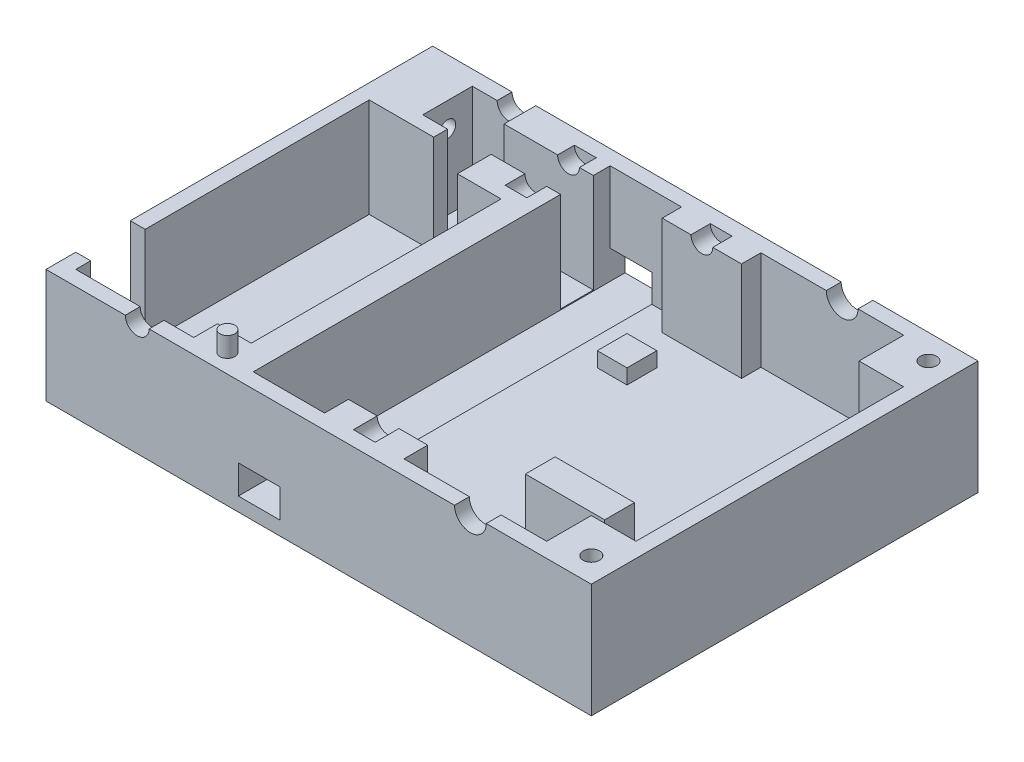
SolidWorks part; units mm, degrees
ref_plane "前视基准面" through (0, 0, 0) normal (0, 0, 1) x (1, 0, 0)
ref_plane "上视基准面" through (0, 0, 0) normal (0, 1, 0) x (1, 0, 0)
ref_plane "右视基准面" through (0, 0, 0) normal (1, 0, 0) x (0, 0, -1)
other "Configuration Table"
sketch "草图1" plane through (0, 0, 0) normal (0, 1, 0) x (1, 0, 0)
  line L1 (-27.5, 19.5) -> (27.5, 19.5)
  line L2 (-27.5, 19.5) -> (-27.5, -19.5)
  line L3 (-27.5, -19.5) -> (27.5, -19.5)
  line L4 (27.5, 19.5) -> (27.5, -19.5)
  line L5 (-27.5, 19.5) -> (27.5, -19.5) construction
  line L6 (-27.5, -19.5) -> (27.5, 19.5) construction
  point P0 (0, 0)
  dimension "D1" = 55
  dimension "D2" = 39
extrude "凸台-拉伸1" add sketch "草图1" along normal blind 11.5
shell "抽壳1" thickness 1.5 removed face at (0, 11.5, 0)
sketch "草图2" plane through (0, 0, -19.5) normal (0, 0, -1) x (-1, 0, 0)
  line L0 (7.9, 1.6) -> (4.1, 1.6) construction
  line L1 (3.9, 4.3) -> (8.1, 4.3)
  line L2 (3.9, 4.3) -> (3.9, 1.4)
  line L3 (3.9, 1.4) -> (8.1, 1.4)
  line L4 (8.1, 4.3) -> (8.1, 1.4)
  line L5 (7.9, 1.6) -> (7.9, 4.1) construction
  line L6 (7.9, 4.1) -> (4.1, 4.1) construction
  line L7 (4.1, 1.6) -> (4.1, 4.1) construction
  circle A0 centre (-15.3, 11.5) radius 1.6
  circle A1 centre (18.3, 11.5) radius 1.2
  circle A2 centre (-15.3, 11.5) radius 1.5 construction
  circle A3 centre (18.3, 11.5) radius 1 construction
  dimension "D1" = 0.1
  dimension "D2" = 0.2
  dimension "D3" = 0.2
  dimension "D4" = 0.2
  dimension "D5" = 0.2
  dimension "D6" = 0.2
extrude "切除-拉伸1" cut sketch "草图2" against normal through all
sketch "草图3" plane through (0, 1.5, 0) normal (0, 1, 0) x (1, 0, 0)
  line L0 (-25.8, -15.5) -> (-10.8, -15.5) construction
  line L5 (-10.7, 9.6) -> (-10.7, -15.6)
  line L6 (-15.1, 13) -> (-8.1, 13)
  line L7 (-15.1, 13) -> (-15.1, 9.6)
  line L8 (-15.1, 9.6) -> (-10.7, 9.6)
  line L10 (-17.1, -18) -> (13.7, -18) construction
  line L11 (-10.7, -18) -> (-8.1, -18)
  line L13 (-14.3, -17.8) -> (-14.3, -15.5) construction
  line L16 (-15.3, 9.5) -> (-15.3, 11.5) construction
  line L17 (-10.8, 9.5) -> (-10.8, -15.5) construction
  line L18 (-8.1, 18) -> (-8.1, -18) construction
  line L19 (13.7, 18) -> (-17.1, 18) construction
  line L20 (-17.1, 18) -> (-8.1, 18)
  line L21 (-17.1, 18) -> (-17.1, 16.3)
  line L22 (-17.1, 16.3) -> (-8.1, 16.3)
  line L23 (-8.1, 18) -> (-8.1, 16.3)
  line L24 (-17.1, 18) -> (-17.1, 19.5) construction
  line L25 (-8.1, 13) -> (-8.1, -18)
  line L26 (4.6159, 15.85) -> (4.2435, 15.85) construction
  line L27 (-0.9, 18) -> (7.1, 18)
  line L28 (-0.9, 18) -> (-0.9, 16.05)
  line L29 (-0.9, 16.05) -> (7.1, 16.05)
  line L30 (7.1, 18) -> (7.1, 16.05)
  line L31 (4.1, -18.1452) -> (4.1, 18.1548) construction
  line L32 (-17.1, -18) -> (13.7, -18) construction
  line L33 (-0.9, -15.6) -> (7.1, -15.6)
  line L34 (-0.9, -15.6) -> (-0.9, -18)
  line L35 (-0.9, -18) -> (7.1, -18)
  line L36 (7.1, -15.6) -> (7.1, -18)
  line L38 (26, 18) -> (16.9, 18) construction
  line L39 (21.5, 18) -> (26, 18)
  line L40 (21.5, 18) -> (21.5, 13.5)
  line L41 (21.5, 13.5) -> (26, 13.5)
  line L42 (26, 18) -> (26, 13.5)
  line L43 (26, -18) -> (26, 18) construction
  line L44 (-26, 18) -> (-26, -18) construction
  line L45 (21.5, -13.5) -> (26, -13.5)
  line L46 (21.5, -13.5) -> (21.5, -18)
  line L47 (21.5, -18) -> (26, -18)
  line L48 (26, -13.5) -> (26, -18)
  line L49 (-26, 18) -> (-22, 18)
  line L50 (-26, 18) -> (-26, 13)
  line L52 (-22, 18) -> (-22, 13)
  line L53 (-26, 11.6) -> (-19.5, 11.6)
  line L54 (-26, 11.6) -> (-26, 13)
  line L55 (-22, 13) -> (-19.5, 13)
  line L56 (-19.5, 11.6) -> (-19.5, 13)
  line L57 (-15.3, 11.5) -> (-21.3, 11.5) construction
  line L58 (-19.3, 19) -> (-19.3, 11.5) construction
  line L59 (-10.8, 9.5) -> (-25.8, 9.5) construction
  line L60 (-19.5, 18) -> (-26, 18) construction
  line L62 (-14.1, -15.6) -> (-10.7, -15.6)
  line L63 (-14.1, -15.6) -> (-14.1, -18)
  line L64 (-14.1, -18) -> (-10.7, -18)
  dimension "D2" = 4
  dimension "D3" = 0.1
  dimension "D4" = 0.2
  dimension "D5" = 1.7
  dimension "D6" = 0.1
  dimension "D7" = 8
  dimension "D8" = 0.2
  dimension "D9" = 3
  dimension "D10" = 8
  dimension "D11" = 3
  dimension "D12" = 2.4
  dimension "D13" = 4.5
  dimension "D14" = 4.5
  dimension "D15" = 4.5
  dimension "D16" = 4.5
  dimension "D17" = 0.2
  dimension "D18" = 0.1
  dimension "D19" = 5
  dimension "D20" = 0.1
  dimension "D21" = 0.2
extrude "凸台-拉伸2" add sketch "草图3" along normal up to surface (10 mm away) up to face at (-23.125, 11.5, 0)
sketch "草图4" plane through (0, 0, 19.5) normal (0, 0, 1) x (1, 0, 0)
  circle A0 centre (3.1, 11.5) radius 1.1
  circle A1 centre (3.1, 11.5) radius 1 construction
  dimension "D1" = 0.1
extrude "切除-拉伸2" cut sketch "草图4" against normal offset from surface (36 mm away) 1.5 from offset 1.5 up to face at (-6, 2.85, -19.5) offset against normal yes
sketch "草图5" plane through (0, 0, -19.5) normal (0, 0, -1) x (-1, 0, 0)
  circle A0 centre (10.6, 11.5) radius 1.1
  circle A1 centre (10.6, 11.5) radius 1 construction
  dimension "D1" = 0.1
extrude "切除-拉伸3" cut sketch "草图5" against normal blind 7 from offset 1.5 offset against normal yes
sketch "草图6" plane through (0, 1.5, 0) normal (0, 1, 0) x (1, 0, 0)
  line L0 (-0.9, 18) -> (-8.1, 18) construction
  line L1 (-1.1, 12.7) -> (1.9, 12.7)
  line L2 (-1.1, 12.7) -> (-1.1, 9.7)
  line L3 (-1.1, 9.7) -> (1.9, 9.7)
  line L4 (1.9, 12.7) -> (1.9, 9.7)
  line L6 (-8.1, -18) -> (-8.1, 13) construction
  line L8 (-32, 4) -> (-27.5, 4)
  line L9 (-32, 4) -> (-32, -4)
  line L10 (-32, -4) -> (-27.5, -4)
  line L11 (-27.5, 4) -> (-27.5, -4)
  line L14 (-27.5, 0) -> (-45.462, 0) construction
  line L15 (-27.5, 19.5) -> (-27.5, -19.5) construction
  dimension "D1" = 8.3
  dimension "D2" = 3
  dimension "D3" = 3
  dimension "D4" = 7
  dimension "D5" = 4.5
  dimension "D6" = 8
extrude "变速卡位凸台-拉伸3" add sketch "草图6" along normal blind 1.5 and the other way blind 1.5
sketch "草图7" plane through (0, 0, 0) normal (0, -1, 0) x (1, 0, 0)
  line L0 (-32, -4) -> (-32, 4) construction
  line L1 (27.5, 0) -> (56.3628, 0) construction
  line L2 (27.5, 19.5) -> (27.5, -19.5) construction
  line L3 (21.5, 13.5) -> (21.5, 18) construction
  line L4 (26, 13.5) -> (21.5, 13.5) construction
  circle A0 centre (-29.8, 0) radius 1
  circle A1 centre (25, 17) radius 0.825
  circle A2 centre (25, -17) radius 0.825
  dimension "D1" = 2
  dimension "D2" = 2.2
  dimension "D3" = 1.65
  dimension "D4" = 3.5
  dimension "D5" = 3.5
extrude "盖子固定切除-拉伸4" cut sketch "草图7" against normal through all
sketch "草图8" plane through (0, 1.5, 0) normal (0, 1, 0) x (1, 0, 0)
  line L0 (27.5, 0) -> (45.6897, 0) construction
  line L1 (27.5, -19.5) -> (27.5, 19.5) construction
  line L2 (26, -13.5) -> (26, 13.5) construction
  line L3 (26, -13.5) -> (21.5, -13.5) construction
  circle A0 centre (23, 7.6) radius 1
  circle A1 centre (23, -10.5) radius 1
  dimension "D1" = 2
  dimension "D2" = 3
  dimension "D3" = 3
  dimension "D4" = 2
  dimension "D5" = 3
  dimension "D6" = 3
extrude "底部螺丝孔切除-拉伸5" cut sketch "草图8" against normal through all
sketch "草图9" plane through (-27.5, 0, 0) normal (-1, 0, 0) x (0, 0, 1)
  line L0 (-19.5, 11.5) -> (19.5, 11.5) construction
  line L1 (-18, 11.5) -> (-18, 1.5) construction
  circle A0 centre (-15.502, 9) radius 0.825
  dimension "D1" = 1.65
  dimension "D2" = 2.5
  dimension "D3" = 2.498
extrude "前螺丝孔切除-拉伸6" cut sketch "草图9" against normal up to next
sketch "草图10" plane through (0, 1.5, 0) normal (0, 1, 0) x (1, 0, 0)
  line L0 (16.8, -26.9936) -> (16.8, 34.2064) construction
  line L1 (11.55, -7.2) -> (19.55, -7.2)
  line L2 (11.55, -7.2) -> (11.55, -10.2)
  line L3 (11.55, -10.2) -> (19.55, -10.2)
  line L4 (19.55, -7.2) -> (19.55, -10.2)
  line L5 (17.8373, -7.1) -> (18.6564, -7.1) construction
  dimension "D1" = 8
  dimension "D2" = 2.75
  dimension "D3" = 0.1
  dimension "D4" = 3
extrude "3mm轴卡位凸台-拉伸4" add sketch "草图10" along normal blind 7
sketch "草图11" plane through (-27.5, 0, 0) normal (-1, 0, 0) x (0, 0, 1)
  line L1 (16.5, 3.5) -> (11, 3.5)
  line L2 (16.5, 3.5) -> (16.5, 11.5)
  line L3 (16.5, 11.5) -> (11, 11.5)
  line L4 (11, 3.5) -> (11, 11.5)
  line L5 (-19.5, 11.5) -> (19.5, 11.5) construction
  line L6 (11, 7.5) -> (11, 3.5) construction
extrude "切除-拉伸4" cut sketch "草图11" against normal up to next
sketch "草图12" plane through (0, 11.5, 0) normal (0, 1, 0) x (1, 0, 0)
  line L0 (-8.1, -18) -> (-8.1, 13) construction
  line L1 (-10.7, -15.6) -> (-14.1, -15.6) construction
  circle A0 centre (-11.1, -17.6) radius 0.75
  dimension "D1" = 1.5
  dimension "D2" = 3
  dimension "D3" = 2
extrude "凸台-拉伸5" add sketch "草图12" along normal blind 2
